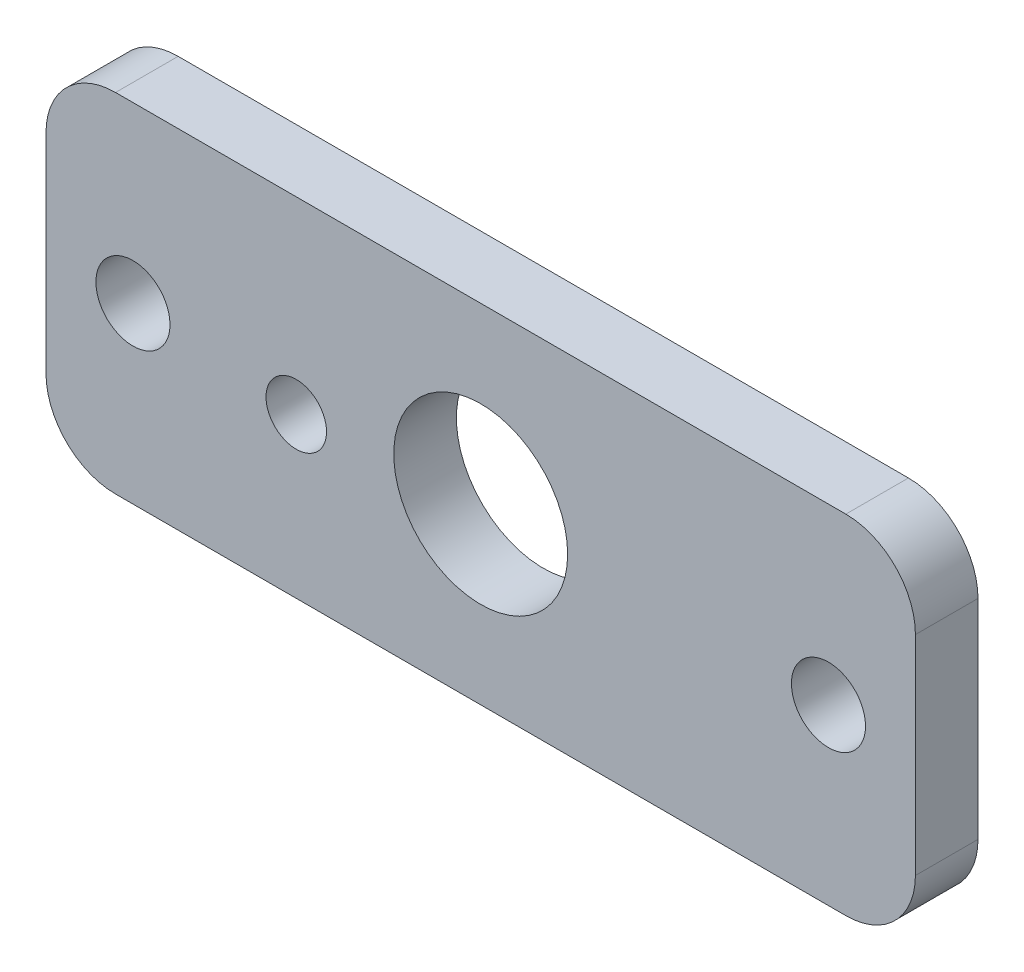
SolidWorks part; units mm, degrees
ref_plane "Front Plane" through (0, 0, 0) normal (0, 0, 1) x (1, 0, 0)
ref_plane "Top Plane" through (0, 0, 0) normal (0, 1, 0) x (1, 0, 0)
ref_plane "Right Plane" through (0, 0, 0) normal (1, 0, 0) x (0, 0, -1)
sketch "Sketch1" plane through (0, 0, 0) normal (0, 0, 1) x (1, 0, 0)
  line L5 (-15.875, -172.466) -> (15.875, -172.466)
  line L6 (-15.875, -172.466) -> (-15.875, -159.766)
  line L7 (-15.875, -159.766) -> (15.875, -159.766)
  line L8 (15.875, -172.466) -> (15.875, -159.766)
  line L9 (-15.875, -172.466) -> (15.875, -159.766) construction
  line L10 (-15.875, -159.766) -> (15.875, -172.466) construction
  point P0 (0, -166.116)
  dimension "D1" = 31.75
  dimension "D2" = 12.7
extrude "Boss-Extrude1" add sketch "Sketch1" along normal blind 2.286
fillet "Fillet1" radius 2.54 4 edges at (15.875, -172.466, 1.143) (-15.875, -172.466, 1.143) (15.875, -159.766, 1.143) (-15.875, -159.766, 1.143)
sketch "Sketch2" plane through (0, 0, 2.286) normal (0, 0, 1) x (1, 0, 0)
  line L0 (-6.3024, -167.6184) -> (-7.1688, -165.6738) construction
  circle A0 centre (0, -166.116) radius 3.175
  circle A1 centre (-6.7356, -166.6461) radius 1.1049
  dimension "D1" = 6.35
  dimension "D2" = 2.2098
extrude "Cut-Extrude1" cut sketch "Sketch2" against normal through all
hole_wizard "#2 Clearance Hole1" positions "Sketch4" profile "Sketch3" hole size "#2" standard "ANSI Inch" end condition through all
sketch "Sketch4" plane through (0, 0, 2.286) normal (0, 0, 1) x (1, 0, 0)
  point P0 (12.7, -166.116)
  point P3 (-12.7, -166.116)
sketch "Sketch3" plane through (12.7, -166.116, 2.286) normal (1, 0, 0) x (0, -1, 0)
  line L0 (0, 0) -> (0, 2.286)
  line L1 (0, 2.286) -> (1.3525, 2.286)
  line L2 (1.3525, 2.286) -> (1.3525, 0)
  line L5 (1.3525, 0) -> (0, 0)
  line L11 (0, -6.35) -> (0, 107.95) construction
  dimension "Thru Hole Dia." = 2.7051
  dimension "Thru Hole Depth" = 2.286
